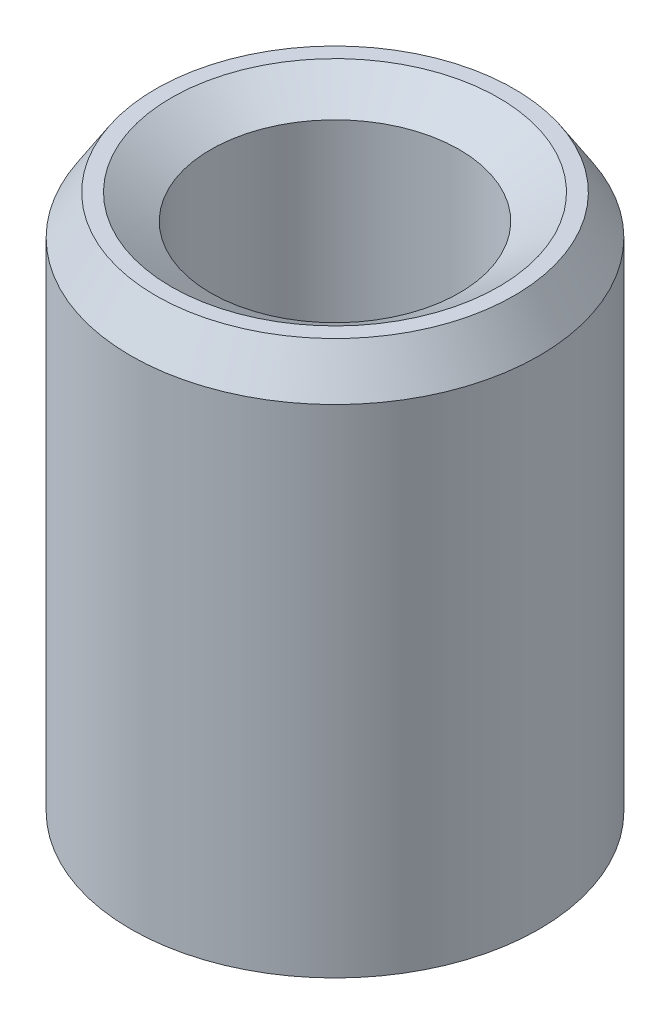
SolidWorks part; units mm, degrees
ref_plane "Front Plane" through (0, 0, 0) normal (0, 0, 1) x (1, 0, 0)
ref_plane "Top Plane" through (0, 0, 0) normal (0, 1, 0) x (1, 0, 0)
ref_plane "Right Plane" through (0, 0, 0) normal (1, 0, 0) x (0, 0, -1)
sketch "Sketch1" plane through (0, 0, 0) normal (0, 1, 0) x (1, 0, 0)
  circle A0 centre (0, 0) radius 7.5
  dimension "SLEEVE_OD" = 15
extrude "Boss-Extrude1" add sketch "Sketch1" along normal blind 20.6025
sketch "Sketch2" plane through (0, 0, 0) normal (0, 1, 0) x (1, 0, 0)
  circle A0 centre (0, 0) radius 4.5632
  dimension "BORE_D" = 9.1264
extrude "Cut-Extrude1" cut sketch "Sketch2" along normal through all
chamfer "Chamfer1" distance 1.4477 angle 32.492 4 edges at (0, 20.6025, 4.5632) (0, 0, 4.5632) (0, 0, 7.5) (0, 20.6025, 7.5) first distance on face at (0, 20.6025, 4.5632) first distance on face at (0, 0, 4.5632) first distance on face at (0, 20.6025, 7.5)
